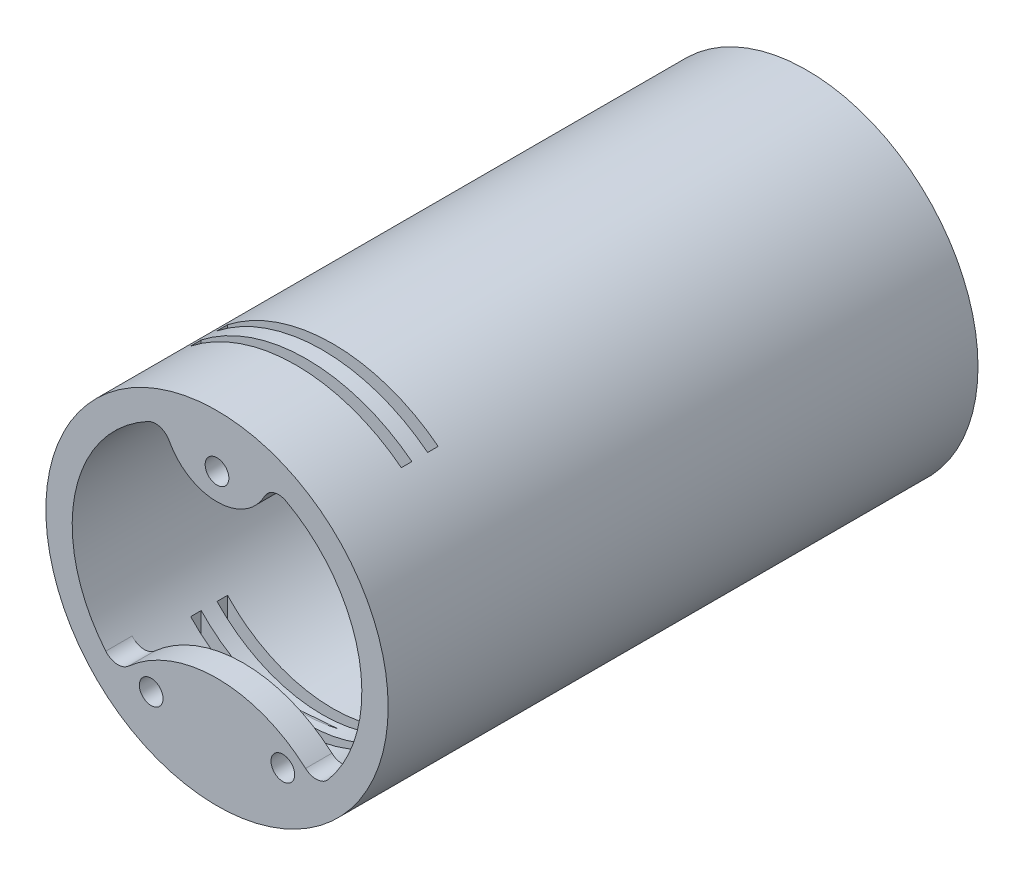
SolidWorks part; units mm, degrees
ref_plane "Alzado" through (0, 0, 0) normal (0, 0, 1) x (1, 0, 0)
ref_plane "Planta" through (0, 0, 0) normal (0, 1, 0) x (1, 0, 0)
ref_plane "Vista lateral" through (0, 0, 0) normal (1, 0, 0) x (0, 0, -1)
sketch "Croquis1" plane through (0, 0, 0) normal (0, 0, 1) x (1, 0, 0)
  circle A0 centre (0, 0) radius 32.5
  circle A1 centre (0, 0) radius 27.5
  dimension "D1" = 65
  dimension "D2" = 5
extrude "Boss-Extrude1" add sketch "Croquis1" along normal blind 112
sketch "Sketch1" plane through (0, 0, 0) normal (0, 0, -1) x (-1, 0, 0)
  line L0 (0, 0) -> (11.3818, 0) construction
  circle A0 centre (-30, 0) radius 1.5
  circle A1 centre (0, 30) radius 1.5
  circle A2 centre (30, 0) radius 1.5
  circle A3 centre (0, -30) radius 1.5
  circle A7 centre (0, 0) radius 30 construction
  circle A8 centre (0, 0) radius 27.5 construction
  point P17 (0, 0)
  dimension "D1" = 2.5
  dimension "D2" = 3
  dimension "D3" = 0
  dimension "D4" = 4
extrude "Cut-Extrude1" cut sketch "Sketch1" against normal blind 5
sketch "Sketch4" plane through (0, 0, 112) normal (0, 0, 1) x (1, 0, 0)
  arc A0 (-10, 25.6174) -> (10, 25.6174) centre (0, 27.7183) ccw
  circle A1 centre (0, 0) radius 27.5 construction
  circle A2 centre (0, 0) radius 27.5 construction
  arc A3 (-10, 25.6174) -> (10, 25.6174) centre (0, 0) cw
  circle A4 centre (0, 0) radius 27.5 construction
  arc A5 (-18.8746, -20) -> (18.8746, -20) centre (0, -36.7059) cw
  arc A6 (-18.8746, -20) -> (18.8746, -20) centre (0, 0) ccw
  point P1 (0, 17.5)
  point P9 (0, 27.5)
  point P11 (0, -27.5)
  point P14 (0, -11.5)
  dimension "D1" = 10
  dimension "D3" = 16
  dimension "D2" = 10
  dimension "D5" = 20
extrude "Boss-Extrude4" add sketch "Sketch4" against normal blind 5
sketch "Sketch2" plane through (0, 0, 112) normal (0, 0, 1) x (1, 0, 0)
  circle A0 centre (-12.5, -20) radius 2.25
  circle A1 centre (12.5, -20) radius 2.25
  circle A2 centre (0, 22.5) radius 2.25
  dimension "D5" = 4.5
  dimension "D6" = 4.5
  dimension "D7" = 4.5
  dimension "D1" = 25
  dimension "D2" = 22.5
  dimension "D3" = 20
  dimension "D4" = 12.5
extrude "Cut-Extrude2" cut sketch "Sketch2" against normal blind 5
fillet "Fillet1" radius 3 4 edges at (18.8746, -20, 109.5) (-18.8746, -20, 109.5) (10, 25.6174, 109.5) (-10, 25.6174, 109.5)
sketch "Sketch5" plane through (0, 0, 0) normal (0, 1, 0) x (1, 0, 0)
  line L0 (-16.8138, -112) -> (16.8138, -112) construction
  line L1 (-20, -97) -> (20, -97)
  line L2 (-20, -97) -> (-20, -95)
  line L3 (-20, -95) -> (20, -95)
  line L4 (20, -97) -> (20, -95)
  line L5 (-20, -97) -> (20, -95) construction
  line L6 (-20, -95) -> (20, -97) construction
  line L7 (-32.5, -112) -> (32.5, -112) construction
  line L9 (-20, -92) -> (20, -92)
  line L10 (-20, -92) -> (-20, -90)
  line L11 (-20, -90) -> (20, -90)
  line L12 (20, -92) -> (20, -90)
  line L13 (-20, -92) -> (20, -90) construction
  line L14 (-20, -90) -> (20, -92) construction
  point P0 (0, -96)
  point P5 (0, 0)
  point P8 (0, -112)
  point P11 (0, -91)
  dimension "D1" = 2
  dimension "D2" = 40
  dimension "D3" = 15
  dimension "D4" = 2
  dimension "D5" = 3
  dimension "D6" = 40
extrude "Cut-Extrude3" cut sketch "Sketch5" against normal mid plane 70
equation "\"D6@Sketch2\"=\"D5@Sketch2\""
equation "\"D7@Sketch2\"=\"D5@Sketch2\""
equation "\"D4@Sketch2\"=\"D1@Sketch2\"/2"
